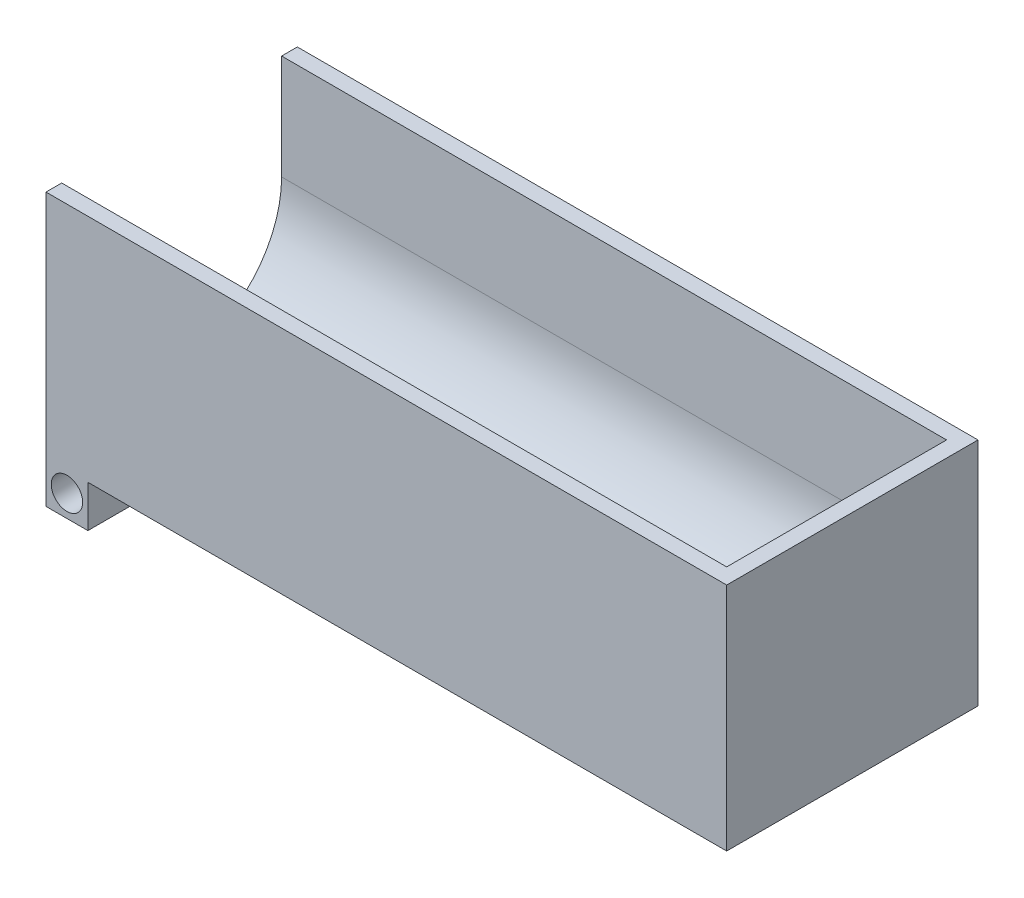
SolidWorks part; units mm, degrees
ref_plane "Front Plane" through (0, 0, 0) normal (0, 0, 1) x (1, 0, 0)
ref_plane "Top Plane" through (0, 0, 0) normal (0, 1, 0) x (1, 0, 0)
ref_plane "Right Plane" through (0, 0, 0) normal (1, 0, 0) x (0, 0, -1)
sketch "Sketch1" plane through (0, 0, 0) normal (1, 0, 0) x (0, 0, -1)
  line L0 (21, 0) -> (24, 0)
  line L1 (24, 0) -> (24, -24)
  line L2 (24, -24) -> (-24, -24)
  line L3 (-24, -24) -> (-24, 0)
  line L4 (-24, 0) -> (-21, 0)
  arc A0 (21, 0) -> (-21, 0) centre (0, 0) cw
  dimension "D3" = 21
  dimension "D1" = 3
  dimension "D2" = 3
  dimension "D4" = 24
extrude "Boss-Extrude1" add sketch "Sketch1" along normal blind 130
sketch "Sketch2" plane through (0, 0, 24) normal (0, 0, 1) x (1, 0, 0)
  line L1 (0, -24) -> (8, -24)
  line L2 (0, -24) -> (0, -32)
  line L3 (0, -32) -> (8, -32)
  line L4 (8, -24) -> (8, -32)
  dimension "D1" = 8
  dimension "D2" = 8
extrude "Boss-Extrude2" add sketch "Sketch2" against normal blind 48
sketch "Sketch3" plane through (0, 0, 24) normal (0, 0, 1) x (1, 0, 0)
  line L0 (0, -32) -> (8, -32) construction
  circle A0 centre (4, -27.8358) radius 3
  point P5 (4, -32)
  dimension "D1" = 6
extrude "Cut-Extrude1" cut sketch "Sketch3" against normal up to next
sketch "Sketch4" plane through (130, 0, 0) normal (1, 0, 0) x (0, 0, -1)
  line L1 (24, 0) -> (-24, 0)
  line L2 (24, 0) -> (24, -24)
  line L3 (24, -24) -> (-24, -24)
  line L4 (-24, 0) -> (-24, -24)
extrude "Boss-Extrude3" add sketch "Sketch4" against normal blind 3
sketch "Sketch5" plane through (0, -24, 0) normal (0, -1, 0) x (1, 0, 0)
  line L0 (130, -24) -> (8, -24) construction
  line L1 (34, -13.3) -> (28, -13.3)
  line L2 (34, -13.3) -> (34, -10.3)
  line L3 (34, -10.3) -> (28, -10.3)
  line L4 (28, -13.3) -> (28, -10.3)
  line L6 (8, -24) -> (8, 24) construction
  dimension "D1" = 10.7
  dimension "D2" = 3
  dimension "D3" = 20
  dimension "D4" = 6
extrude "Boss-Extrude4" add sketch "Sketch5" along normal blind 5
sketch "Sketch6" plane through (0, 0, -10.3) normal (0, 0, 1) x (1, 0, 0)
  line L0 (28, -29) -> (34, -29) construction
  circle A0 centre (31, -26.5) radius 0.75
  point P4 (31, -29)
  dimension "D1" = 1.5
  dimension "D2" = 2.5
extrude "Cut-Extrude2" cut sketch "Sketch6" against normal through all
sketch "Sketch7" plane through (0, 0, 0) normal (0, 1, 0) x (1, 0, 0)
  line L8 (130, 24) -> (0, 24)
  line L9 (0, 24) -> (0, 21)
  line L10 (0, 21) -> (127, 21)
  line L11 (127, 21) -> (127, -21)
  line L12 (127, -21) -> (0, -21)
  line L13 (0, -21) -> (0, -24)
  line L14 (0, -24) -> (130, -24)
  line L15 (130, -24) -> (130, 24)
  line L16 (130, 24) -> (0, 24)
  line L17 (0, 24) -> (0, 21)
  line L18 (0, 21) -> (127, 21)
  line L19 (127, 21) -> (127, -21)
  line L20 (127, -21) -> (0, -21)
  line L21 (0, -21) -> (0, -24)
  line L22 (0, -24) -> (130, -24)
  line L23 (130, -24) -> (130, 24)
  dimension "D1" = 0
extrude "Boss-Extrude5" add sketch "Sketch7" along normal blind 20
